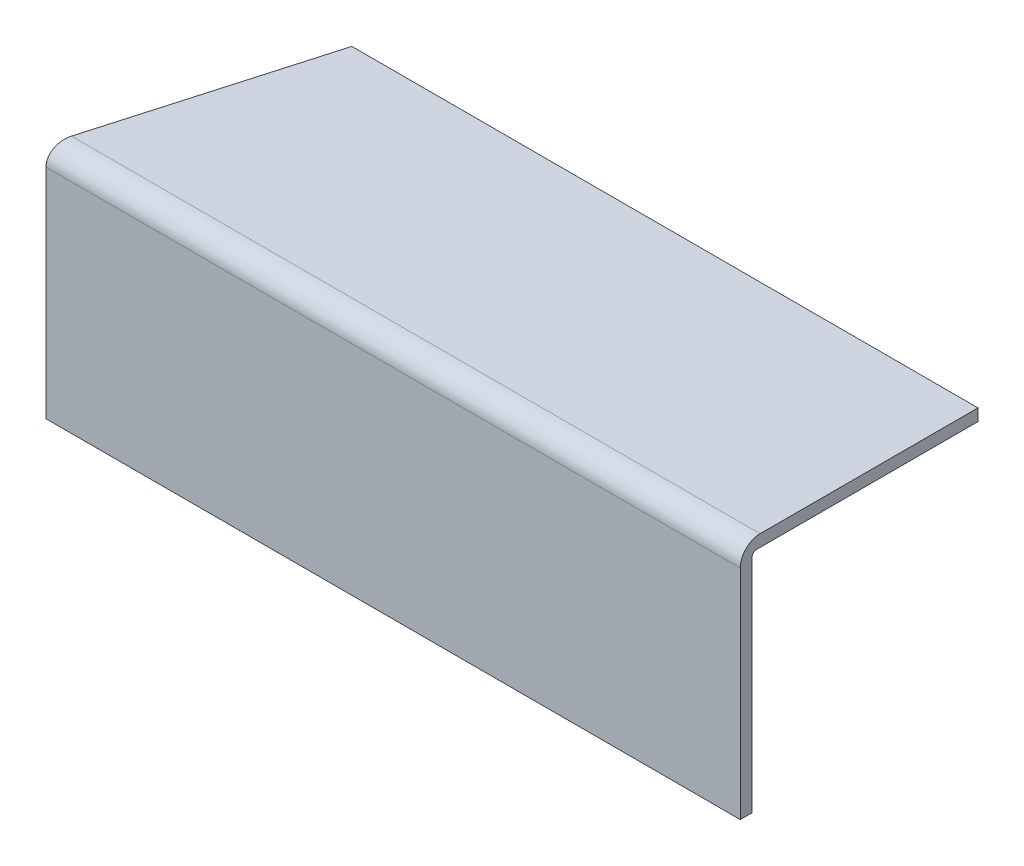
SolidWorks part; units mm, degrees
material "201 Annealed Stainless Steel (SS)"
ref_plane "Front Plane" through (0, 0, 0) normal (0, 0, 1) x (1, 0, 0)
ref_plane "Top Plane" through (0, 0, 0) normal (0, 1, 0) x (1, 0, 0)
ref_plane "Right Plane" through (0, 0, 0) normal (1, 0, 0) x (0, 0, -1)
sketch "Sketch1" plane through (0, 0, 0) normal (1, 0, 0) x (0, 0, -1)
  line L0 (0, 0) -> (0, 60)
  line L1 (0, 0) -> (60, 0)
  line L2 (60, 0) -> (60, 3)
  line L3 (60, 3) -> (3, 3)
  line L4 (3, 3) -> (3, 60)
  line L5 (3, 60) -> (0, 60)
  dimension "D1" = 60
  dimension "D2" = 60
  dimension "D3" = 3
extrude "Boss-Extrude1" add sketch "Sketch1" along normal mid plane 175.25
fillet "Fillet1" radius 5 1 edges at (0, 0, 0)
fillet "Fillet2" radius 1 1 edges at (0, 3, -3)
sketch "Sketch2" plane through (0, 0, 0) normal (0, -1, 0) x (1, 0, 0)
  line L0 (-100.1527, 43.6893) -> (-57.1185, -106.3888)
  line L1 (-57.1185, -106.3888) -> (-93.9231, -116.9424)
  line L2 (-93.9231, -116.9424) -> (-136.9573, 33.1357)
  line L3 (-136.9573, 33.1357) -> (-100.1527, 43.6893)
  line L5 (-87.625, -5) -> (-87.625, -60) construction
  dimension "D1" = 16
extrude "Cut-Extrude1" cut sketch "Sketch2" against normal through all
mirror "Mirror1" about plane through (87.625, 60, -3) normal (0, -1, 0) of bodies 102
delete or keep bodies "Body-Delete/Keep 1" type delete bodies bodies 102
